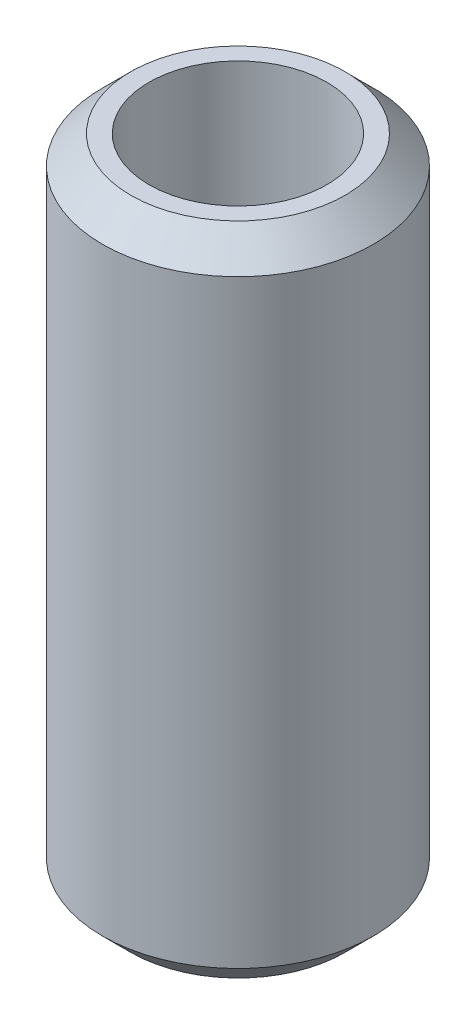
SolidWorks part; units mm, degrees
ref_plane "Front Plane" through (0, 0, 0) normal (0, 0, 1) x (1, 0, 0)
ref_plane "Top Plane" through (0, 0, 0) normal (0, 1, 0) x (1, 0, 0)
ref_plane "Right Plane" through (0, 0, 0) normal (1, 0, 0) x (0, 0, -1)
sketch "Sketch1" plane through (0, 0, 0) normal (0, 1, 0) x (1, 0, 0)
  circle A0 centre (0, 0) radius 22.5
  dimension "SHAFT_OD" = 45
extrude "Boss-Extrude1" add sketch "Sketch1" along normal blind 108.9239
sketch "Sketch2" plane through (0, 0, 0) normal (0, 1, 0) x (1, 0, 0)
  circle A0 centre (0, 0) radius 14.765
  dimension "BORE_D" = 29.53
extrude "Cut-Extrude1" cut sketch "Sketch2" along normal through all
chamfer "Chamfer1" distance 4.7002 angle 45 2 edges at (0, 108.9239, 22.5) (0, 0, 22.5)
